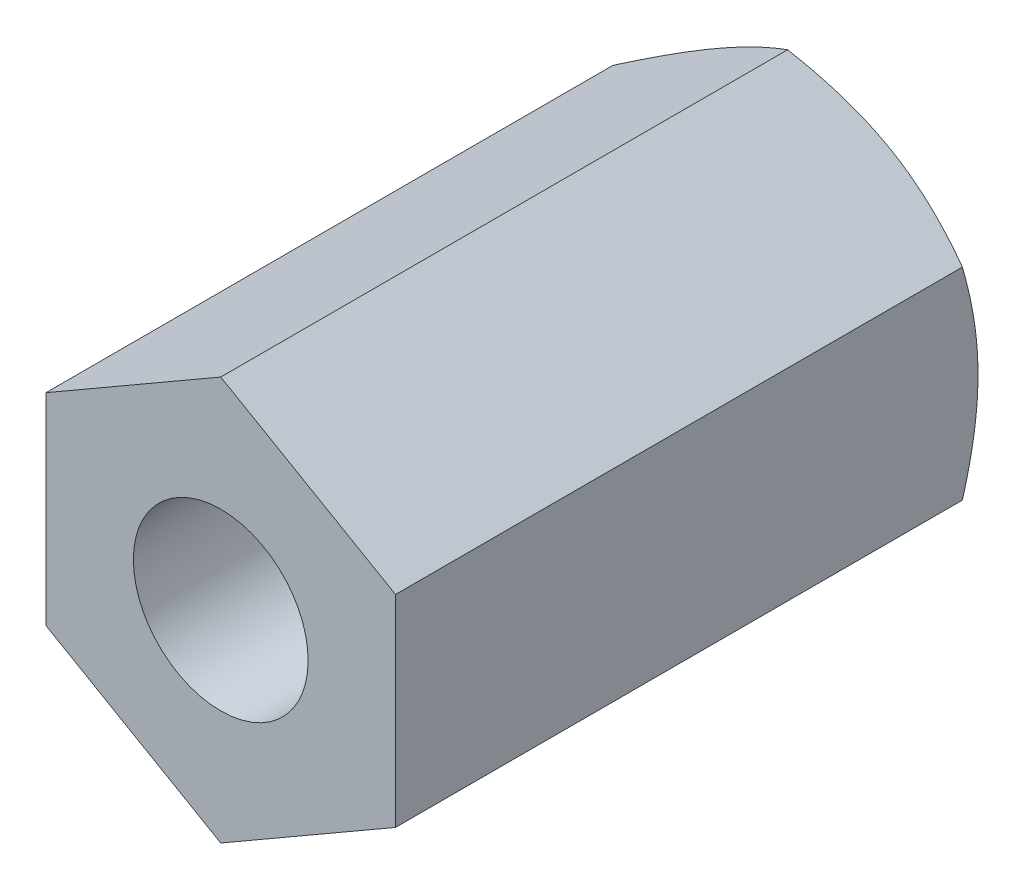
SolidWorks part; units mm, degrees
ref_plane "Front Plane" through (0, 0, 0) normal (0, 0, 1) x (1, 0, 0)
ref_plane "Top Plane" through (0, 0, 0) normal (0, 1, 0) x (1, 0, 0)
ref_plane "Right Plane" through (0, 0, 0) normal (1, 0, 0) x (0, 0, -1)
sketch "Sketch3" plane through (0, 0, 0) normal (1, 0, 0) x (0, 0, -1)
  line L0 (-5, 0) -> (5, 0) construction
  line L1 (0, 3) -> (0, -3) construction
  line L2 (-5, 1.5) -> (-5, -1.5) construction
  point P2 (0.2, 0)
  point P3 (-0.2, 0)
  dimension "Length" = 10
  dimension "Min Thread Length" = 4.8
  dimension "D1" = 4.8
  dimension "Thread Dia" = 3
  dimension "Hex" = 6
sketch "Sketch1" plane through (0, 0, 0) normal (0, 0, 1) x (1, 0, 0)
  line L1 (0, 3.4641) -> (-3, 1.7321)
  line L2 (-3, 1.7321) -> (-3, -1.7321)
  line L3 (-3, -1.7321) -> (0, -3.4641)
  line L4 (0, -3.4641) -> (3, -1.7321)
  line L5 (3, -1.7321) -> (3, 1.7321)
  line L6 (3, 1.7321) -> (0, 3.4641)
  circle A0 centre (0, 0) radius 3 construction
  circle A1 centre (0, 0) radius 1.5
extrude "Extrude1" add sketch "Sketch1" along normal up to vertex (5 mm away) and the other way up to vertex (5 mm away) up to point (0, 0, 5) other way up to point (0, 0, -5)
cosmetic thread "Cosmetic Thread1" parameters "D2"=4
sketch "Sketch11" plane through (0, 0, -5) normal (0, 0, -1) x (-1, 0, 0)
  circle A0 centre (0, 0) radius 1.5 construction
  circle A1 centre (0, 0) radius 1.5
curve "Helix/Spiral1" [suppressed] pitch 0.5 height 10.5 turns 21 parameters "Pitch"=0.5
sketch "Sketch12" plane through (0, 0, 0) normal (1, 0, 0) x (0, 0, -1)
  line L0 (5.4375, 1.5) -> (5, 1.5)
  line L1 (5.4375, 1.5) -> (5.25, 1.1752)
  line L2 (5.25, 1.1752) -> (5.1875, 1.1752)
  line L3 (5.1875, 1.1752) -> (5, 1.5)
  line L4 (5.2187, 1.1752) -> (5.2187, 1.5) construction
  line L5 (5.3437, 1.3376) -> (5.0937, 1.3376) construction
  dimension "D1" = 0.0625
  dimension "D2" = 0.25
  dimension "D3" = 60
sweep "Sweep1" [suppressed] add profiles "Sketch12" path "Helix/Spiral1"
sketch "Sketch6" plane through (0, 0, -5) normal (0, 0, -1) x (-1, 0, 0)
  line L6 (0, 3.4641) -> (-3, 1.7321)
  line L7 (-3, 1.7321) -> (-3, -1.7321)
  line L8 (-3, -1.7321) -> (0, -3.4641)
  line L9 (0, -3.4641) -> (3, -1.7321)
  line L10 (3, -1.7321) -> (3, 1.7321)
  line L11 (3, 1.7321) -> (0, 3.4641)
  line L12 (0, 3.4641) -> (-3, 1.7321)
  line L13 (-3, 1.7321) -> (-3, -1.7321)
  line L14 (-3, -1.7321) -> (0, -3.4641)
  line L15 (0, -3.4641) -> (3, -1.7321)
  line L16 (3, -1.7321) -> (3, 1.7321)
  line L17 (3, 1.7321) -> (0, 3.4641)
  dimension "D1" = 0
extrude "Extrude2" [suppressed] cut sketch "Sketch6" along normal through all
sketch "Sketch7" plane through (0, 0, -5) normal (0, 0, -1) x (-1, 0, 0)
  circle A2 centre (0, 0) radius 1.5508
  circle A3 centre (0, 0) radius 1.5508
  dimension "D1" = 0.0508
extrude "Extrude3" cut sketch "Sketch7" against normal through all draft 43
sketch "Sketch8" plane through (0, 0, -5) normal (0, 0, -1) x (-1, 0, 0)
  circle A0 centre (0, 0) radius 3 construction
  circle A1 centre (0, 0) radius 3
extrude "Extrude4" cut sketch "Sketch8" against normal through all draft 60 flip side to cut
mirror "Mirror1" [suppressed] about plane through (0, 0, 0) normal (0, 0, 1)
sketch "Sketch9" [suppressed] plane through (0, 0, 0) normal (1, 0, 0) x (0, 0, -1)
  line L1 (-1.2, 1.1353) -> (1.2, 1.1353)
  line L2 (-1.2, 1.1353) -> (-1.2, 0)
  line L3 (-1.2, 0) -> (1.2, 0)
  line L4 (1.2, 1.1353) -> (1.2, 0)
  line L7 (-6, 0) -> (6, 0) construction
revolve "Revolve" [suppressed] add sketch "Sketch9" angle 360 about L0
sketch "Sketch10" [suppressed] plane through (0, 0, 0) normal (1, 0, 0) x (0, 0, -1)
  line L0 (6, 1.25) -> (1.2, 1.25)
  line L1 (-6, 1.25) -> (-1.2, 1.25)
  line L2 (1.2, 1.25) -> (1.2, -1.25)
  line L3 (-6, -1.25) -> (-1.2, -1.25)
  line L4 (-1.2, 1.25) -> (-1.2, -1.25)
  line L5 (1.2, -1.25) -> (6, -1.25)
equation "\"D1@Sketch3\" = \"Min Thread Length@Sketch3\""
equation "\"D3@Helix/Spiral1\" = \"Length@Sketch3\"+\"Pitch@Helix/Spiral1\""
equation "\"D1@Sketch12\" = \"Pitch@Helix/Spiral1\"*.125"
equation "\"D2@Sketch12\" = \"Pitch@Helix/Spiral1\"*.5"
